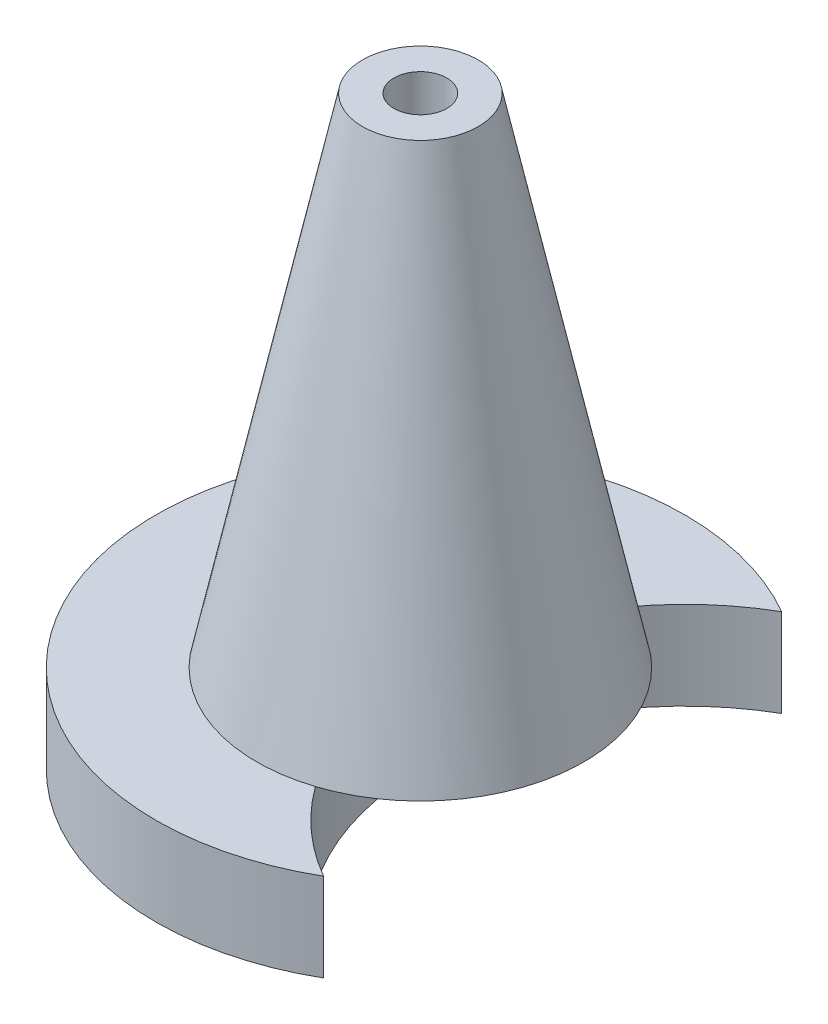
SolidWorks part; units mm, degrees
ref_plane "정면" through (0, 0, 0) normal (0, 0, 1) x (1, 0, 0)
ref_plane "윗면" through (0, 0, 0) normal (0, 1, 0) x (1, 0, 0)
ref_plane "우측면" through (0, 0, 0) normal (1, 0, 0) x (0, 0, -1)
sketch "스케치1" plane through (0, 0, 0) normal (0, 1, 0) x (1, 0, 0)
  circle A0 centre (0, 0) radius 18.55
  dimension "D1" = 37.1
ref_plane "평면1" through (0, 56.41, 0) normal (0, 1, 0) x (1, 0, 0)
sketch "스케치2" plane through (0, 56.41, 0) normal (0, 1, 0) x (1, 0, 0)
  circle A0 centre (0, 0) radius 6.56
  dimension "D1" = 13.12
loft "로프트1" add profiles "스케치2", "스케치1" connector at (0.0495, 56.41, 6.5598) connector at (-0.0778, 0, 18.5498)
sketch "스케치3" plane through (0, 0, 0) normal (0, 1, 0) x (1, 0, 0)
  circle A0 centre (0, 0) radius 30
  circle A2 centre (30, 0) radius 30
  dimension "D1" = 60
  dimension "D2" = 60
extrude "보스-돌출2" add sketch "스케치3" against normal blind 10 contours A0
extrude "컷-돌출2" cut sketch "스케치3<5>" against normal blind 10 contours A0 A2 region at (15, 0, 0)
sketch "스케치3<5>" plane through (0, 0, 0) normal (0, 1, 0) x (1, 0, 0) same geometry as "스케치3"
sketch "스케치4" plane through (0, 56.41, 0) normal (0, 1, 0) x (1, 0, 0)
  circle A0 centre (0, 0) radius 3
  dimension "D1" = 6
extrude "컷-돌출3" cut sketch "스케치4" against normal blind 22
